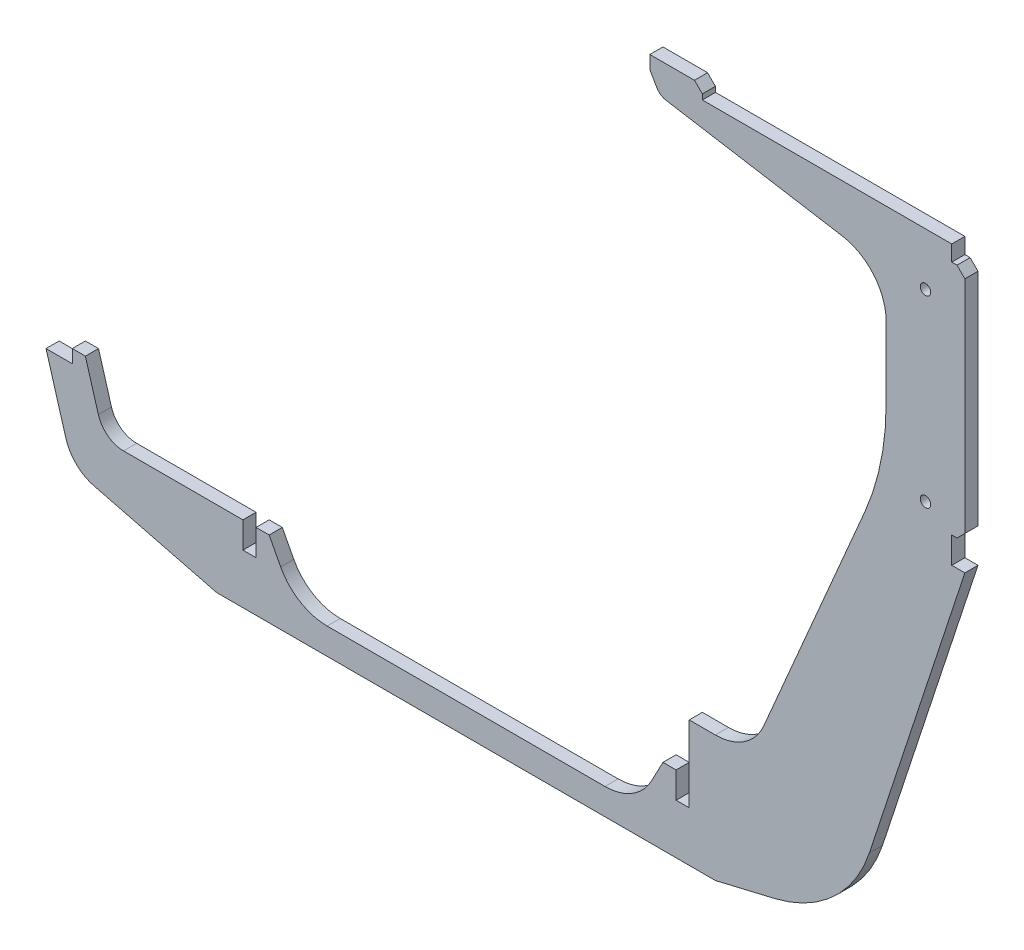
SolidWorks part; units mm, degrees
material "Stal węglowa"
ref_plane "Front" through (0, 0, 0) normal (0, 0, 1) x (1, 0, 0)
ref_plane "Top" through (0, 0, 0) normal (0, 1, 0) x (1, 0, 0)
ref_plane "Right" through (0, 0, 0) normal (1, 0, 0) x (0, 0, -1)
sketch "Szkic1" plane through (0, 0, 0) normal (0, 0, 1) x (1, 0, 0)
  line L0 (81.709, -73.8262) -> (-108.291, -73.8262)
  line L1 (-108.291, -73.8262) -> (-154.993, -61.9951)
  line L2 (-98.291, -44.8262) -> (-143.7595, -44.8262)
  line L3 (-93.291, -44.8262) -> (-93.291, -54.8262)
  line L4 (-93.291, -54.8262) -> (-98.291, -54.8262)
  line L5 (-98.291, -54.8262) -> (-98.291, -44.8262)
  line L6 (-93.291, -44.8262) -> (-88.291, -44.8262)
  line L7 (-83.9147, -53.1412) -> (-88.291, -44.8262)
  line L8 (39.6344, -63.8262) -> (-66.2164, -63.8262)
  line L9 (66.709, -44.8262) -> (66.709, -54.8262)
  line L10 (66.709, -54.8262) -> (71.709, -54.8262)
  line L11 (66.709, -44.8262) -> (61.709, -44.8262)
  line L12 (57.3327, -53.1412) -> (61.709, -44.8262)
  line L13 (71.709, -54.8262) -> (71.709, -25.8262)
  line L14 (71.709, -25.8262) -> (81.6639, -25.8262)
  line L15 (81.709, -73.8262) -> (104.3788, -68.4422)
  line L16 (138.6235, 76.3076) -> (100.0468, -13.7046)
  line L17 (176.709, 75.1738) -> (140.3204, -35.4223)
  line L18 (176.709, 172.1738) -> (176.709, 88.1738)
  line L19 (146.709, 143.2312) -> (146.709, 115.6995)
  line L20 (62.87, 174.1469) -> (129.997, 162.9591)
  line L21 (56.709, 186.1738) -> (56.709, 181.1738)
  line L22 (56.709, 186.1738) -> (73.709, 186.1738)
  line L23 (171.709, 75.1738) -> (171.709, 85.1738)
  line L24 (171.709, 85.1738) -> (173.709, 85.1738)
  line L25 (176.709, 75.1738) -> (171.709, 75.1738)
  line L26 (171.709, 175.1738) -> (173.709, 175.1738)
  line L27 (171.709, 181.1738) -> (171.709, 175.1738)
  line L28 (76.709, 181.1738) -> (171.709, 181.1738)
  line L29 (76.709, 183.1738) -> (76.709, 181.1738)
  line L30 (-163.291, -20.8262) -> (-158.291, -20.8262)
  line L31 (-173.291, -25.8262) -> (-163.291, -25.8262)
  line L32 (-173.291, -25.8262) -> (-165.702, -51.6793)
  line L33 (-163.291, -25.8262) -> (-163.291, -20.8262)
  line L34 (-158.291, -20.8262) -> (-153.3546, -37.6428)
  line L35 (173.709, 85.1738) -> (176.709, 88.1738)
  line L36 (173.709, 175.1738) -> (176.709, 172.1738)
  line L37 (73.709, 186.1738) -> (76.709, 183.1738)
  line L38 (56.709, 181.1738) -> (59.3618, 176.5789)
  arc A0 (-83.9147, -53.1412) -> (-66.2164, -63.8262) centre (-66.2164, -43.8262) ccw
  arc A1 (39.6344, -63.8262) -> (57.3327, -53.1412) centre (39.6344, -43.8262) ccw
  arc A2 (104.3788, -68.4422) -> (140.3204, -35.4223) centre (92.8251, -19.7953) ccw
  arc A3 (138.6235, 76.3076) -> (146.709, 115.6995) centre (46.709, 115.6995) ccw
  arc A4 (146.709, 143.2312) -> (129.997, 162.9591) centre (126.709, 143.2312) ccw
  arc A5 (81.6639, -25.8262) -> (100.0468, -13.7046) centre (81.6639, -5.8262) ccw
  arc A6 (-165.702, -51.6793) -> (-154.993, -61.9951) centre (-151.3093, -47.4544) ccw
  arc A7 (-153.3546, -37.6428) -> (-143.7595, -44.8262) centre (-143.7595, -34.8262) ccw
  circle A8 centre (161.709, 91.1738) radius 2
  circle A9 centre (161.709, 161.1738) radius 2
  arc A10 (59.3618, 176.5789) -> (62.87, 174.1469) centre (63.692, 179.0789) ccw
extrude "Dodanie-wyciągnięcie1" add sketch "Szkic1" along normal blind 5
